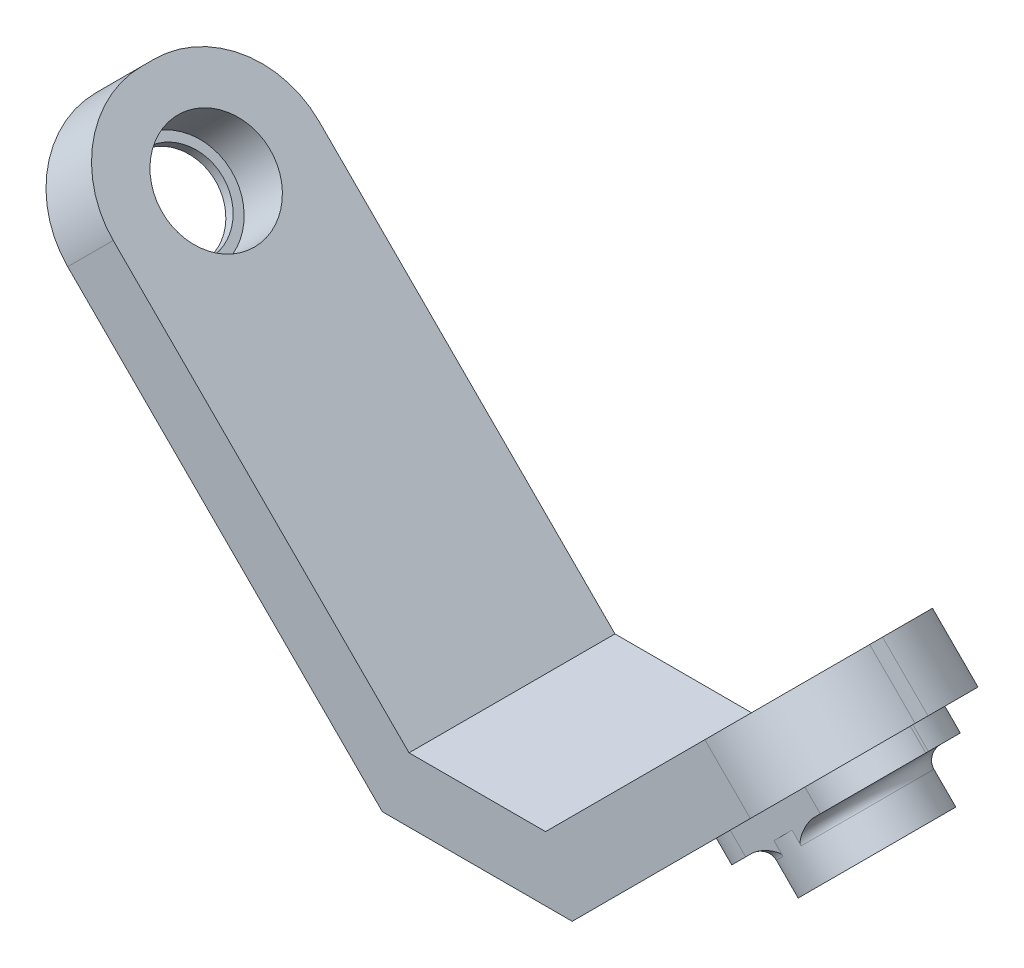
SolidWorks part; units mm, degrees
ref_plane "正面" through (0, 0, 0) normal (0, 0, 1) x (1, 0, 0)
ref_plane "平面" through (0, 0, 0) normal (0, 1, 0) x (1, 0, 0)
ref_plane "右側面" through (0, 0, 0) normal (1, 0, 0) x (0, 0, -1)
sketch "ｽｹｯﾁ1" plane through (0, 0, 0) normal (0, 0, 1) x (1, 0, 0)
  line L0 (0, 0) -> (-29.7487, 29.7487)
  line L1 (-29.7487, 29.7487) -> (-26.2132, 33.2843)
  line L2 (-26.2132, 33.2843) -> (2.0711, 5)
  line L3 (2.0711, 5) -> (12.6777, 5)
  line L4 (12.6777, 5) -> (30.3553, 22.6777)
  line L5 (30.3553, 22.6777) -> (33.8909, 19.1421)
  line L6 (33.8909, 19.1421) -> (14.7487, 0)
  line L7 (14.7487, 0) -> (0, 0)
  point P6 (21.5165, 13.8388)
  point P10 (-20.9099, 27.981)
  dimension "D1" = 135
  dimension "D2" = 135
  dimension "D3" = 5
  dimension "D4" = 5
  dimension "D5" = 5
  dimension "D6" = 7.5
  dimension "D7" = 45
  dimension "D9" = 25
  dimension "D8" = 25
extrude "ﾎﾞｽ - 押し出し1" add sketch "ｽｹｯﾁ1" along normal mid plane 16
fillet "ﾌｨﾚｯﾄ1" radius 7.5 4 edges at (32.1231, 20.9099, -8) (32.1231, 20.9099, 8) (-27.981, 31.5165, -8) (-27.981, 31.5165, 8)
sketch "ｽｹｯﾁ2" plane through (0, 0, 0) normal (-0.7071, -0.7071, 0) x (0, 0, 1)
  line L1 (0.5, 42.0711) -> (-0.5, 42.0711) construction
  circle A0 centre (0, 34.5711) radius 4.2
  dimension "D1" = 8.4
  dimension "D2" = 7.5
extrude "ｶｯﾄ - 押し出し1" cut sketch "ｽｹｯﾁ2" along normal blind 4.2 from surface starting at face at (-15.3835, 22.4545, 0)
sketch "ｽｹｯﾁ3" plane through (7.3744, -7.3744, 0) normal (0.7071, -0.7071, 0) x (0, 0, -1)
  line L0 (-0.5, 37.5) -> (0.5, 37.5) construction
  line L1 (-6.5, 21) -> (6.5, 21) construction
  line L2 (6.5, 21) -> (6.5, 34) construction
  line L3 (6.5, 34) -> (-6.5, 34) construction
  line L4 (-6.5, 34) -> (-6.5, 21) construction
  line L6 (0.1, 36.5) -> (-0.1, 36.5)
  line L7 (5, 31.6) -> (5, 23.4)
  line L8 (0.1, 18.5) -> (-0.1, 18.5)
  line L9 (-5, 31.6) -> (-5, 23.4)
  line L10 (5, 36.5) -> (-5, 18.5) construction
  line L11 (5, 18.5) -> (-5, 36.5) construction
  circle A0 centre (0, 27.5) radius 6.5 construction
  arc A1 (0.1, 36.5) -> (5, 31.6) centre (0.1, 31.6) cw
  arc A2 (5, 23.4) -> (0.1, 18.5) centre (0.1, 23.4) cw
  arc A3 (-0.1, 36.5) -> (-5, 31.6) centre (-0.1, 31.6) ccw
  arc A4 (-0.1, 18.5) -> (-5, 23.4) centre (-0.1, 23.4) cw
  point P7 (0, 37.5)
  dimension "D2" = 13
  dimension "D5" = 4.9
  dimension "D1" = 10
  dimension "D3" = 10
  dimension "D4" = 18
extrude "ｶｯﾄ - 押し出し2" cut sketch "ｽｹｯﾁ3" against normal blind 2.5
sketch "ｽｹｯﾁ5" plane through (5.6066, -5.6066, 0) normal (0.7071, -0.7071, 0) x (0, 0, -1)
  line L0 (-0.5, 37.5) -> (0.5, 37.5) construction
  circle A0 centre (0, 27.5) radius 1.9
  point P5 (0, 37.5)
  dimension "D2" = 3.8
  dimension "D1" = 10
extrude "ｶｯﾄ - 押し出し5" cut sketch "ｽｹｯﾁ5" against normal through all
sketch "ｽｹｯﾁ6" plane through (5.6066, -5.6066, 0) normal (0.7071, -0.7071, 0) x (0, 0, -1)
  line L0 (-0.1, 36.4) -> (0.1, 36.4)
  line L6 (-4.9, 31.6) -> (-4.9, 23.4)
  line L7 (-4.9, 31.6) -> (-4.9, 23.4)
  line L8 (-0.1, 18.6) -> (0.1, 18.6)
  line L9 (-0.1, 18.6) -> (0.1, 18.6)
  line L10 (4.9, 23.4) -> (4.9, 31.6)
  line L16 (4.9, 23.4) -> (4.9, 31.6)
  line L18 (0.1, 36.4) -> (-0.1, 36.4)
  circle A0 centre (0, 27.5) radius 1.9 construction
  circle A1 centre (0, 27.5) radius 1.9
  arc A6 (-0.1, 36.4) -> (-4.9, 31.6) centre (-0.1, 31.6) ccw
  arc A7 (-0.1, 36.4) -> (-4.9, 31.6) centre (-0.1, 31.6) ccw
  arc A8 (-4.9, 23.4) -> (-0.1, 18.6) centre (-0.1, 23.4) ccw
  arc A9 (-4.9, 23.4) -> (-0.1, 18.6) centre (-0.1, 23.4) ccw
  arc A10 (0.1, 18.6) -> (4.9, 23.4) centre (0.1, 23.4) ccw
  arc A11 (0.1, 18.6) -> (4.9, 23.4) centre (0.1, 23.4) ccw
  arc A12 (4.9, 31.6) -> (0.1, 36.4) centre (0.1, 31.6) ccw
  arc A13 (4.9, 31.6) -> (0.1, 36.4) centre (0.1, 31.6) ccw
  dimension "D1" = 0.1
extrude "ﾎﾞｽ - 押し出し2" add sketch "ｽｹｯﾁ6" along normal blind 4 from offset 0.2 separate body
sketch "ｽｹｯﾁ12" plane through (8.5765, -8.5765, 0) normal (0.7071, -0.7071, 0) x (0, 0, -1)
  circle A0 centre (0, 27.5) radius 5
  dimension "D1" = 10
extrude "ﾎﾞｽ - 押し出し3" add sketch "ｽｹｯﾁ12" along normal blind 3.4
sketch "ｽｹｯﾁ7" plane through (10.9806, -10.9806, 0) normal (0.7071, -0.7071, 0) x (0, 0, -1)
  line L0 (-2.6375, 27.1375) -> (-3, 27.5) construction
  line L1 (-3, 27.5) -> (-2.6375, 27.8625) construction
  line L2 (0, 27.5) -> (-2.6375, 27.1375) construction
  line L3 (0, 27.5) -> (-2.6375, 27.8625) construction
  line L4 (0, 27.5) -> (-3, 27.5) construction
  line L5 (-2.6375, 27.1375) -> (-2.95, 27.45)
  line L6 (-2.95, 27.45) -> (-3.95, 27.45)
  line L7 (-2.95, 27.45) -> (-2.95, 27.55) construction
  line L8 (-2.95, 27.55) -> (-3.95, 27.55)
  line L9 (-3.95, 27.45) -> (-3.95, 27.55)
  line L10 (-2.95, 27.55) -> (-2.6375, 27.8625)
  line L11 (-2.6375, 27.8625) -> (-2.8541, 28.2478)
  line L12 (-2.8541, 28.2478) -> (-3.817, 28.5176)
  line L13 (-2.8271, 28.344) -> (-3.79, 28.6138)
  line L14 (-3.817, 28.5176) -> (-3.79, 28.6138)
  line L15 (-2.8271, 28.344) -> (-2.4419, 28.5607)
  line L16 (-2.4419, 28.5607) -> (-2.5465, 28.9901)
  line L17 (-2.5465, 28.9901) -> (-3.4009, 29.5096)
  line L18 (-2.4946, 29.0755) -> (-3.349, 29.5951)
  line L19 (-3.4009, 29.5096) -> (-3.349, 29.5951)
  line L20 (-2.4946, 29.0755) -> (-2.0652, 29.1801)
  line L21 (-2.0652, 29.1801) -> (-2.0501, 29.6218)
  line L22 (-2.0501, 29.6218) -> (-2.7326, 30.3527)
  line L23 (-1.977, 29.6901) -> (-2.6595, 30.4209)
  line L24 (-2.7326, 30.3527) -> (-2.6595, 30.4209)
  line L25 (-1.977, 29.6901) -> (-1.5353, 29.675)
  line L26 (-1.5353, 29.675) -> (-1.4016, 30.0963)
  line L27 (-1.4016, 30.0963) -> (-1.8617, 30.9841)
  line L28 (-1.3128, 30.1423) -> (-1.7729, 31.0301)
  line L29 (-1.8617, 30.9841) -> (-1.7729, 31.0301)
  line L30 (-1.3128, 30.1423) -> (-0.8915, 30.0086)
  line L31 (-0.8915, 30.0086) -> (-0.6491, 30.3781)
  line L32 (-0.6491, 30.3781) -> (-0.8526, 31.3572)
  line L33 (-0.5512, 30.3985) -> (-0.7547, 31.3776)
  line L34 (-0.8526, 31.3572) -> (-0.7547, 31.3776)
  line L35 (-0.5512, 30.3985) -> (-0.1817, 30.1561)
  line L36 (-0.1817, 30.1561) -> (0.1514, 30.4465)
  line L37 (0.1514, 30.4465) -> (0.2197, 31.4442)
  line L38 (0.2512, 30.4397) -> (0.3194, 31.4374)
  line L39 (0.2197, 31.4442) -> (0.3194, 31.4374)
  line L40 (0.2512, 30.4397) -> (0.5417, 30.1066)
  line L41 (0.5417, 30.1066) -> (0.9408, 30.2964)
  line L42 (0.9408, 30.2964) -> (1.2757, 31.2387)
  line L43 (1.035, 30.2629) -> (1.3699, 31.2052)
  line L44 (1.2757, 31.2387) -> (1.3699, 31.2052)
  line L45 (1.035, 30.2629) -> (1.2248, 29.8638)
  line L46 (1.2248, 29.8638) -> (1.6604, 29.9389)
  line L47 (1.6604, 29.9389) -> (2.237, 30.7559)
  line L48 (1.7421, 29.8812) -> (2.3187, 30.6982)
  line L49 (2.237, 30.7559) -> (2.3187, 30.6982)
  line L50 (1.7421, 29.8812) -> (1.8171, 29.4457)
  line L51 (1.8171, 29.4457) -> (2.2568, 29.4005)
  line L52 (2.2568, 29.4005) -> (3.0325, 30.0316)
  line L53 (2.3199, 29.3229) -> (3.0956, 29.954)
  line L54 (3.0325, 30.0316) -> (3.0956, 29.954)
  line L55 (2.3199, 29.3229) -> (2.2747, 28.8833)
  line L56 (2.2747, 28.8833) -> (2.6859, 28.7211)
  line L57 (2.6859, 28.7211) -> (3.6031, 29.1195)
  line L58 (2.7257, 28.6294) -> (3.6429, 29.0278)
  line L59 (3.6031, 29.1195) -> (3.6429, 29.0278)
  line L60 (2.7257, 28.6294) -> (2.5636, 28.2183)
  line L61 (2.5636, 28.2183) -> (2.9157, 27.9512)
  line L62 (2.9157, 27.9512) -> (3.9064, 28.0874)
  line L63 (2.9293, 27.8522) -> (3.92, 27.9883)
  line L64 (3.9064, 28.0874) -> (3.92, 27.9883)
  line L65 (2.9293, 27.8522) -> (2.6623, 27.5)
  line L66 (2.6623, 27.5) -> (2.9293, 27.1478)
  line L67 (2.9293, 27.1478) -> (3.92, 27.0117)
  line L68 (2.9157, 27.0488) -> (3.9064, 26.9126)
  line L69 (3.92, 27.0117) -> (3.9064, 26.9126)
  line L70 (2.9157, 27.0488) -> (2.5636, 26.7817)
  line L71 (2.5636, 26.7817) -> (2.7257, 26.3706)
  line L72 (2.7257, 26.3706) -> (3.6429, 25.9722)
  line L73 (2.6859, 26.2789) -> (3.6031, 25.8805)
  line L74 (3.6429, 25.9722) -> (3.6031, 25.8805)
  line L75 (2.6859, 26.2789) -> (2.2747, 26.1167)
  line L76 (2.2747, 26.1167) -> (2.3199, 25.6771)
  line L77 (2.3199, 25.6771) -> (3.0956, 25.046)
  line L78 (2.2568, 25.5995) -> (3.0325, 24.9684)
  line L79 (3.0956, 25.046) -> (3.0325, 24.9684)
  line L80 (2.2568, 25.5995) -> (1.8171, 25.5543)
  line L81 (1.8171, 25.5543) -> (1.7421, 25.1188)
  line L82 (1.7421, 25.1188) -> (2.3187, 24.3018)
  line L83 (1.6604, 25.0611) -> (2.237, 24.2441)
  line L84 (2.3187, 24.3018) -> (2.237, 24.2441)
  line L85 (1.6604, 25.0611) -> (1.2248, 25.1362)
  line L86 (1.2248, 25.1362) -> (1.035, 24.7371)
  line L87 (1.035, 24.7371) -> (1.3699, 23.7948)
  line L88 (0.9408, 24.7036) -> (1.2757, 23.7613)
  line L89 (1.3699, 23.7948) -> (1.2757, 23.7613)
  line L90 (0.9408, 24.7036) -> (0.5417, 24.8934)
  line L91 (0.5417, 24.8934) -> (0.2512, 24.5603)
  line L92 (0.2512, 24.5603) -> (0.3194, 23.5626)
  line L93 (0.1514, 24.5535) -> (0.2197, 23.5558)
  line L94 (0.3194, 23.5626) -> (0.2197, 23.5558)
  line L95 (0.1514, 24.5535) -> (-0.1817, 24.8439)
  line L96 (-0.1817, 24.8439) -> (-0.5512, 24.6015)
  line L97 (-0.5512, 24.6015) -> (-0.7547, 23.6224)
  line L98 (-0.6491, 24.6219) -> (-0.8526, 23.6428)
  line L99 (-0.7547, 23.6224) -> (-0.8526, 23.6428)
  line L100 (-0.6491, 24.6219) -> (-0.8915, 24.9914)
  line L101 (-0.8915, 24.9914) -> (-1.3128, 24.8577)
  line L102 (-1.3128, 24.8577) -> (-1.7729, 23.9699)
  line L103 (-1.4016, 24.9037) -> (-1.8617, 24.0159)
  line L104 (-1.7729, 23.9699) -> (-1.8617, 24.0159)
  line L105 (-1.4016, 24.9037) -> (-1.5353, 25.325)
  line L106 (-1.5353, 25.325) -> (-1.977, 25.3099)
  line L107 (-1.977, 25.3099) -> (-2.6595, 24.5791)
  line L108 (-2.0501, 25.3782) -> (-2.7326, 24.6473)
  line L109 (-2.6595, 24.5791) -> (-2.7326, 24.6473)
  line L110 (-2.0501, 25.3782) -> (-2.0652, 25.8199)
  line L111 (-2.0652, 25.8199) -> (-2.4946, 25.9245)
  line L112 (-2.4946, 25.9245) -> (-3.349, 25.4049)
  line L113 (-2.5465, 26.0099) -> (-3.4009, 25.4904)
  line L114 (-3.349, 25.4049) -> (-3.4009, 25.4904)
  line L115 (-2.5465, 26.0099) -> (-2.4419, 26.4393)
  line L116 (-2.4419, 26.4393) -> (-2.8271, 26.656)
  line L117 (-2.8271, 26.656) -> (-3.79, 26.3862)
  line L118 (-2.8541, 26.7522) -> (-3.817, 26.4824)
  line L119 (-3.79, 26.3862) -> (-3.817, 26.4824)
  line L120 (-2.8541, 26.7522) -> (-2.6375, 27.1375)
  circle A0 centre (0, 27.5) radius 3 construction
  circle A1 centre (0, 27.5) radius 2.6623 construction
  point P147 (0, 27.5)
  dimension "D1" = 6
  dimension "D2" = 7.826
  dimension "D3" = 7.826
  dimension "D4" = 0.1
  dimension "D5" = 1
  dimension "D6" = 23
extrude "ｶｯﾄ - 押し出し6" cut sketch "ｽｹｯﾁ7" against normal blind 3.4
sketch "ｽｹｯﾁ9" plane through (8.5765, -8.5765, 0) normal (0.7071, -0.7071, 0) x (0, 0, -1)
  circle A0 centre (0, 20.5) radius 1.4
  circle A1 centre (0, 34.5) radius 1.4
  circle A3 centre (0, 27.5) radius 1.9 construction
  point P4 (0, 23.5)
  point P5 (0, 0)
  point P8 (0, 0)
  point P9 (0, 0)
  dimension "D1" = 2.8
  dimension "D3" = 7
  dimension "D2" = 14
extrude "ｶｯﾄ - 押し出し7" cut sketch "ｽｹｯﾁ9" against normal through all
sketch "ｽｹｯﾁ10" plane through (8.5765, -8.5765, 0) normal (0.7071, -0.7071, 0) x (0, 0, -1)
  line L19 (-0.75, 20.5) -> (-0.375, 19.8505)
  line L20 (-0.375, 19.8505) -> (0.375, 19.8505)
  line L21 (0.375, 19.8505) -> (0.75, 20.5)
  line L22 (0.75, 20.5) -> (0.375, 21.1495)
  line L23 (0.375, 21.1495) -> (-0.375, 21.1495)
  line L24 (-0.375, 21.1495) -> (-0.75, 20.5)
  line L25 (-0.75, 34.5) -> (-0.375, 33.8505)
  line L26 (-0.375, 33.8505) -> (0.375, 33.8505)
  line L27 (0.375, 33.8505) -> (0.75, 34.5)
  line L28 (0.75, 34.5) -> (0.375, 35.1495)
  line L29 (0.375, 35.1495) -> (-0.375, 35.1495)
  line L30 (-0.375, 35.1495) -> (-0.75, 34.5)
  circle A0 centre (0, 20.5) radius 0.6495 construction
  circle A1 centre (0, 34.5) radius 1.4
  circle A3 centre (0, 34.5) radius 1.4 construction
  circle A5 centre (0, 20.5) radius 1.4
  circle A7 centre (0, 20.5) radius 1.4 construction
  circle A8 centre (0, 34.5) radius 0.6495 construction
  point P0 (0, 0)
  dimension "D3" = 1.5
  dimension "D1" = 0
  dimension "D2" = 0
extrude "ｶｯﾄ - 押し出し8" cut sketch "ｽｹｯﾁ10" against normal through all
sketch "ｽｹｯﾁ11" plane through (0.5657, 0.5657, 0) normal (-0.7071, -0.7071, 0) x (0, 0, 1)
  circle A0 centre (0, 34.5711) radius 3.5
  dimension "D1" = 7
extrude "ｶｯﾄ - 押し出し9" cut sketch "ｽｹｯﾁ11" along normal blind 10
fillet "ﾌｨﾚｯﾄ2" radius 1 2 edges at (24.4864, 7.3335, 0) (31.5574, 14.4045, 0)
equation "\"D4@ｽｹｯﾁ1\"=\"D3@ｽｹｯﾁ1\""
equation "\"D5@ｽｹｯﾁ1\"=\"D3@ｽｹｯﾁ1\""
equation "\"D2@ｽｹｯﾁ7\"=360deg/46"
equation "\"D3@ｽｹｯﾁ7\"=\"D2@ｽｹｯﾁ7\""
equation "\"D2@ｽｹｯﾁ9\"=\"D3@ｽｹｯﾁ9\"*2"
